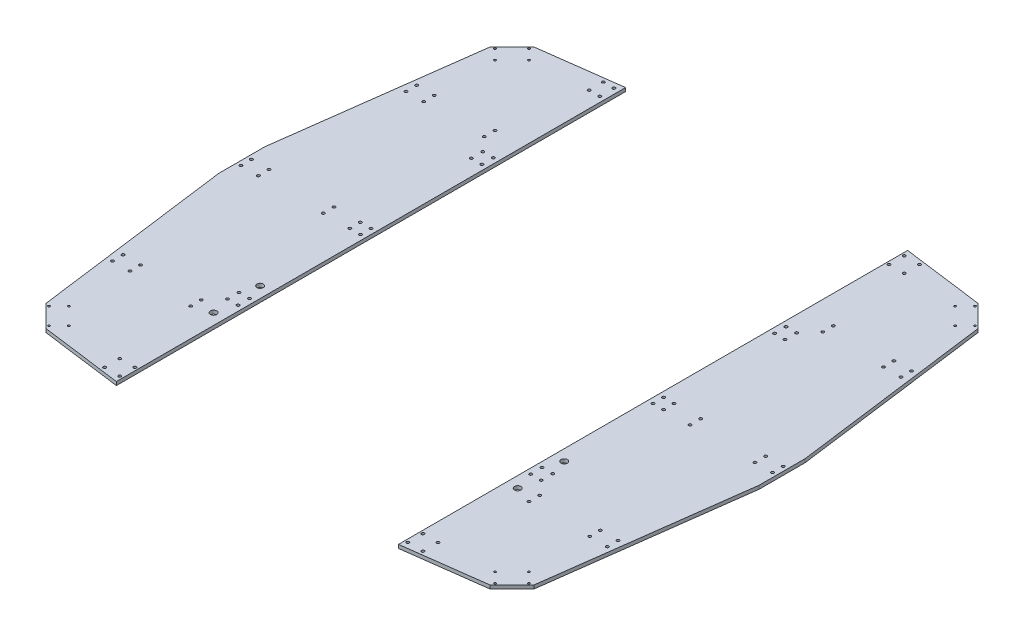
SolidWorks part; units mm, degrees
ref_plane "前视基准面" through (0, 0, 0) normal (0, 0, 1) x (1, 0, 0)
ref_plane "上视基准面" through (0, 0, 0) normal (0, 1, 0) x (1, 0, 0)
ref_plane "右视基准面" through (0, 0, 0) normal (1, 0, 0) x (0, 0, -1)
other "Configuration Table"
sketch "草图1" plane through (0, 0, 0) normal (0, 1, 0) x (1, 0, 0)
  line L0 (-314.9222, 345.9222) -> (-345.9222, 314.9222)
  line L5 (325, -325) -> (-325, 325) construction
  line L6 (325, 325) -> (-325, -325) construction
  line L7 (0, 325) -> (0, -325) construction
  line L8 (-383.07, 0) -> (383.0748, 0) construction
  line L9 (314.9222, 345.9222) -> (32.7201, 383.0748)
  line L10 (314.9222, 345.9222) -> (345.9222, 314.9222)
  line L11 (-383.07, 13.0001) -> (-230, 13.0001) construction
  line L12 (-314.9222, 345.9222) -> (-32.7201, 383.0748)
  line L13 (0, 325) -> (0, 399.6983)
  line L14 (-32.7201, 383.0748) -> (32.7201, 383.0748)
  line L15 (314.9222, -345.9222) -> (32.7201, -383.0748)
  line L16 (-32.7201, -383.0748) -> (32.7201, -383.0748)
  line L17 (-314.9222, -345.9222) -> (-32.7201, -383.0748)
  line L18 (-314.9222, -345.9222) -> (-345.9222, -314.9222)
  line L19 (-345.9222, 314.9222) -> (-383.0748, 32.7201)
  line L20 (-383.0748, -32.7201) -> (-383.0748, 32.7201)
  line L21 (-345.9222, -314.9222) -> (-383.0748, -32.7201)
  line L22 (-345.9222, -314.9222) -> (-314.9222, -345.9222)
  line L23 (345.9222, -314.9222) -> (314.9222, -345.9222)
  line L24 (345.9222, -314.9222) -> (383.0748, -32.7201)
  line L25 (383.0748, 32.7201) -> (383.0748, -32.7201)
  line L26 (345.9222, 314.9222) -> (383.0748, 32.7201)
  line L27 (-383.07, -12.9999) -> (-230, -12.9999) construction
  line L29 (361.6863, 195.182) -> (230, 195.182) construction
  line L30 (358.2633, 221.182) -> (230, 221.182) construction
  line L31 (-358.2633, 221.182) -> (-230, 221.182) construction
  line L32 (-361.6863, 195.182) -> (-230, 195.182) construction
  line L33 (361.6863, -195.182) -> (230, -195.182) construction
  line L34 (358.2633, -221.182) -> (230, -221.182) construction
  line L35 (-361.6863, -195.182) -> (-230, -195.182) construction
  line L36 (-358.2633, -221.182) -> (-230, -221.182) construction
  line L37 (-228, -357.3657) -> (-228, 357.3618) construction
  line L38 (-202, -360.7887) -> (-202, 360.7847) construction
  line L39 (383.07, 13.0001) -> (230, 13.0001) construction
  circle A5 centre (0, 0) radius 250
  circle A6 centre (302.1379, 326.1795) radius 1.5
  circle A7 centre (316.28, 340.3217) radius 1.5
  circle A8 centre (340.3217, 316.28) radius 1.5
  circle A9 centre (326.1795, 302.1379) radius 1.5
  circle A10 centre (302.1379, -326.1795) radius 1.5
  circle A11 centre (316.28, -340.3217) radius 1.5
  circle A12 centre (326.1795, -302.1379) radius 1.5
  circle A13 centre (340.3217, -316.28) radius 1.5
  circle A14 centre (-326.1795, -302.1379) radius 1.5
  circle A15 centre (-340.3217, -316.28) radius 1.5
  circle A16 centre (-302.1379, -326.1795) radius 1.5
  circle A17 centre (-316.28, -340.3217) radius 1.5
  circle A18 centre (-302.1379, 326.1795) radius 1.5
  circle A19 centre (-316.28, 340.3217) radius 1.5
  circle A20 centre (-326.1795, 302.1379) radius 1.5
  circle A21 centre (-340.3217, 316.28) radius 1.5
  circle A22 centre (350.9184, 215.682) radius 2
  circle A23 centre (377.0748, 7.5001) radius 2
  circle A24 centre (350.9184, 200.682) radius 2
  circle A25 centre (325.9184, 215.682) radius 2
  circle A26 centre (325.9184, 200.682) radius 2
  circle A27 centre (377.0748, -7.5951) radius 2
  circle A28 centre (352.0748, 7.5001) radius 2
  circle A29 centre (352.0748, -7.5951) radius 2
  circle A30 centre (350.9184, -200.682) radius 2
  circle A31 centre (350.9184, -215.682) radius 2
  circle A32 centre (325.9184, -200.682) radius 2
  circle A33 centre (325.9184, -215.682) radius 2
  circle A34 centre (-350.9184, -200.682) radius 2
  circle A35 centre (-325.9184, -200.682) radius 2
  circle A36 centre (-350.9184, -215.682) radius 2
  circle A37 centre (-325.9184, -215.682) radius 2
  circle A38 centre (-377.0748, 7.5001) radius 2
  circle A39 centre (-352.0748, 7.5001) radius 2
  circle A40 centre (-377.0748, -7.4999) radius 2
  circle A41 centre (-352.0748, -7.4999) radius 2
  circle A42 centre (-350.9184, 215.682) radius 2
  circle A43 centre (-350.9184, 200.682) radius 2
  circle A44 centre (-325.9184, 215.682) radius 2
  circle A45 centre (-325.9184, 200.682) radius 2
  circle A46 centre (-222.5, -164.8255) radius 2
  circle A47 centre (-207.5, -164.8255) radius 2
  circle A48 centre (-222.5, -181.0301) radius 2
  circle A49 centre (-207.5, -181.0301) radius 2
  circle A50 centre (-222.5, 181.0301) radius 2
  circle A51 centre (-207.5, 164.8255) radius 2
  circle A52 centre (-222.5, 164.8255) radius 2
  circle A53 centre (-207.5, 181.0301) radius 2
  circle A54 centre (207.5, -164.8255) radius 2
  circle A55 centre (222.5, -164.8255) radius 2
  circle A56 centre (207.5, -181.0301) radius 2
  circle A57 centre (222.5, -181.0301) radius 2
  circle A58 centre (207.5, 164.8255) radius 2
  circle A59 centre (222.5, 164.8255) radius 2
  circle A60 centre (207.5, 181.0301) radius 2
  circle A61 centre (222.5, 181.0301) radius 2
  circle A62 centre (-240, 215.682) radius 2
  circle A63 centre (-240, 200.682) radius 2
  circle A64 centre (-260, 7.5) radius 2
  circle A65 centre (-260, -7.5) radius 2
  circle A66 centre (-240, -200.682) radius 2
  circle A67 centre (-240, -215.682) radius 2
  circle A68 centre (240, -215.682) radius 2
  circle A69 centre (240, -200.682) radius 2
  circle A72 centre (240, 200.682) radius 2
  circle A73 centre (240, 215.682) radius 2
  circle A74 centre (207.5, 9.4052) radius 2
  circle A75 centre (222.5, 9.4052) radius 2
  circle A76 centre (207.5, -5.5948) radius 2
  circle A77 centre (222.5, -5.5948) radius 2
  circle A78 centre (-222.5, -5.5948) radius 2
  circle A79 centre (-207.5, -5.5948) radius 2
  circle A80 centre (-222.5, 9.4052) radius 2
  circle A81 centre (-207.5, 9.4052) radius 2
  circle A82 centre (260, -7.5) radius 2
  circle A83 centre (260, 7.5) radius 2
  circle A84 centre (215.6127, -141.5543) radius 4.5
  circle A85 centre (215.6127, -207.5543) radius 4.5
  circle A86 centre (-215.6127, -207.5543) radius 4.5
  circle A87 centre (-215.6127, -141.5543) radius 4.5
  point P0 (0, 0)
  point P13 (0, 383.0748)
  point P24 (-330.4222, -330.4222)
  point P75 (0, 0)
  dimension "D6" = 25
  dimension "D7" = 15
  dimension "D8" = 500
  dimension "D5" = 4
  dimension "D13" = 6
  dimension "D14" = 6
  dimension "D15" = 6
  dimension "D16" = 6
  dimension "D17" = 25
  dimension "D20" = 8
  dimension "D21" = 25
  dimension "D23" = 8
  dimension "D28" = 5.5
  dimension "D29" = 5.5
  dimension "D30" = 5.5
  dimension "D31" = 5.5
  dimension "D32" = 5.5
  dimension "D33" = 5.5
  dimension "D35" = 5.5
  dimension "D37" = 5.5
  dimension "D1" = 650
  dimension "D2" = 650
  dimension "D3" = 31
  dimension "D4" = 142.5
  dimension "D9" = 5.5
  dimension "D10" = 5.5
  dimension "D11" = 25
  dimension "D12" = 25
  dimension "D22" = 25
  dimension "D24" = 25
  dimension "D25" = 25
  dimension "D26" = 25
  dimension "D27" = 5.5
  dimension "D34" = 5.5
  dimension "D36" = 5.5
  dimension "D38" = 7.5001
  dimension "D39" = 7.4999
  dimension "D40" = 7.5
  dimension "D41" = 7.5
extrude "凸台-拉伸2" add sketch "草图1" along normal blind 5 contours L26 L10 L9 L14 L12 L0 L19 L20 L21 L18 L17 L16 L15 L23 L24 L25 | A13 L22 | L22 | A13 L18 region at (-172.4069, 0, -353.7562)
sketch "草图2" plane through (0, 5, 0) normal (0, 1, 0) x (1, 0, 0)
  line L0 (0, 0) -> (-330.4222, -330.4222) construction
  line L1 (0, 383.0748) -> (0, -383.0748)
  line L2 (-32.7201, 383.0748) -> (32.7201, 383.0748) construction
  line L3 (-32.7201, -383.0748) -> (32.7201, -383.0748) construction
  line L4 (-200, 361.052) -> (-200, -361.052)
  line L5 (-314.9222, 345.9222) -> (-32.7201, 383.0748) construction
  line L6 (-314.9222, -345.9222) -> (-32.7201, -383.0748) construction
  line L7 (200, 361.052) -> (200, -361.052)
  line L8 (314.9222, 345.9222) -> (32.7201, 383.0748) construction
  line L9 (314.9222, -345.9222) -> (32.7201, -383.0748) construction
  line L10 (-200, 361.052) -> (-200, 484.7149)
  line L11 (-200, 484.7149) -> (200, 484.7149)
  line L12 (200, 484.7149) -> (200, 361.052)
  line L13 (-200, -361.052) -> (-200, -418.819)
  line L14 (-200, -418.819) -> (200, -418.819)
  line L15 (200, -418.819) -> (200, -361.052)
  dimension "D1" = 200
  dimension "D2" = 200
extrude "切除-拉伸1" cut sketch "草图2" against normal blind 122 and the other way through all contours L4 L1 | L7 L1 | L7 L1 | L4 L1 | L0 L4 region at (-190.1188, 5, -422.8834)
sketch "草图3" plane through (0, 0, 0) normal (0, -1, 0) x (-1, 0, 0)
  circle A0 centre (225.7527, -352.0225) radius 2
  circle A1 centre (204.2473, -352.0225) radius 2
  circle A2 centre (225.7527, -330.517) radius 2
  circle A3 centre (204.2473, -330.517) radius 2
extrude "切除-拉伸2" cut sketch "草图3" along normal through all and the other way blind 39 contours A0 | A1 | A2 | A3
sketch "草图4" plane through (0, 5, 0) normal (0, 1, 0) x (1, 0, 0)
  line L0 (-222.5, 352.0186) -> (-207.5, 352.0186)
  line L1 (-215, 352.0186) -> (-215, 337.3883)
  line L2 (-228, -357.3657) -> (-228, 357.3618) construction
  line L3 (-202, -360.7887) -> (-202, 360.7847) construction
  line L4 (-228, -357.3657) -> (-228, 357.3618)
  line L5 (-202, -360.7887) -> (-202, 360.7847)
  line L6 (-202, 337.3883) -> (-228, 337.3883)
  circle A0 centre (-222.5, 352.0186) radius 2
  circle A1 centre (-207.5, 352.0186) radius 2
  circle A2 centre (-222.5, 332.0186) radius 2
  circle A3 centre (-207.5, 332.0186) radius 2
  circle A4 centre (204.2473, 330.5131) radius 2
  circle A5 centre (225.7527, 330.5131) radius 2
  circle A6 centre (204.2473, 352.0186) radius 2
  circle A7 centre (225.7527, 352.0186) radius 2
  circle A8 centre (204.2473, -352.0225) radius 2
  circle A9 centre (225.7527, -352.0225) radius 2
  circle A10 centre (204.2473, -330.517) radius 2
  circle A11 centre (225.7527, -330.517) radius 2
  point P3 (-215, 337.3883)
  point P19 (0, 0)
  point P20 (0, 0)
  point P21 (0, 0)
  point P24 (0, 0)
  dimension "D1" = 4
  dimension "D2" = 15
  dimension "D3" = 20
extrude "切除-拉伸3" cut sketch "草图4" against normal through all and the other way blind 20 contours A8 | A9 | A11 | A4 | A6 | A5 | A7 | A1 | A0 | A2 | A3 | A10 region at (-207.5, 5, -353.962) region at (-224.4434, 5, -352.0186) region at (-222.5, 5, -332.0186) region at (-207.5, 5, -332.0186) region at (204.2473, 5, -330.5131) region at (225.7527, 5, -330.5131) region at (204.2473, 5, -352.0186) region at (225.7527, 5, -352.0186) region at (204.2473, 5, 352.0225) region at (225.7527, 5, 352.0225) region at (225.7527, 5, 330.517)
sketch "草图5" plane through (0, 5, 0) normal (0, 1, 0) x (1, 0, 0)
  line L0 (-200, 150) -> (-200, -150)
  line L1 (200, 150) -> (200, -150)
  line L2 (-260, 7.5) -> (-260, -7.5) construction
  line L3 (-260, -7.5) -> (-200, -7.5) construction
  line L4 (-200, -7.5) -> (-200, 7.5)
  line L5 (-200, 7.5) -> (-260, 7.5) construction
  line L6 (-228, -357.3657) -> (-228, 357.3618) construction
  line L7 (-202, -360.7887) -> (-202, 360.7847) construction
  line L8 (0, 250) -> (0, -250) construction
  line L9 (-200, 361.048) -> (-200, -361.052) construction
  circle A0 centre (0, 0) radius 250
  circle A1 centre (-222.5, 7.5) radius 2
  circle A2 centre (-207.5, 7.5) radius 2
  circle A3 centre (-222.5, -7.5) radius 2
  circle A4 centre (-207.5, -7.5) radius 2
  circle A5 centre (207.5, -7.5) radius 2
  circle A6 centre (222.5, -7.5) radius 2
  circle A7 centre (207.5, 7.5) radius 2
  circle A8 centre (222.5, 7.5) radius 2
  dimension "D1" = 5.5
  dimension "D2" = 5.5
  dimension "D3" = 5.5
  dimension "D4" = 5.5
extrude "凸台-拉伸3" add sketch "草图5" against normal blind 5 contours L0 | L1 A0 region at (-220.2076, 5, 0) region at (220.2076, 5, 0)
